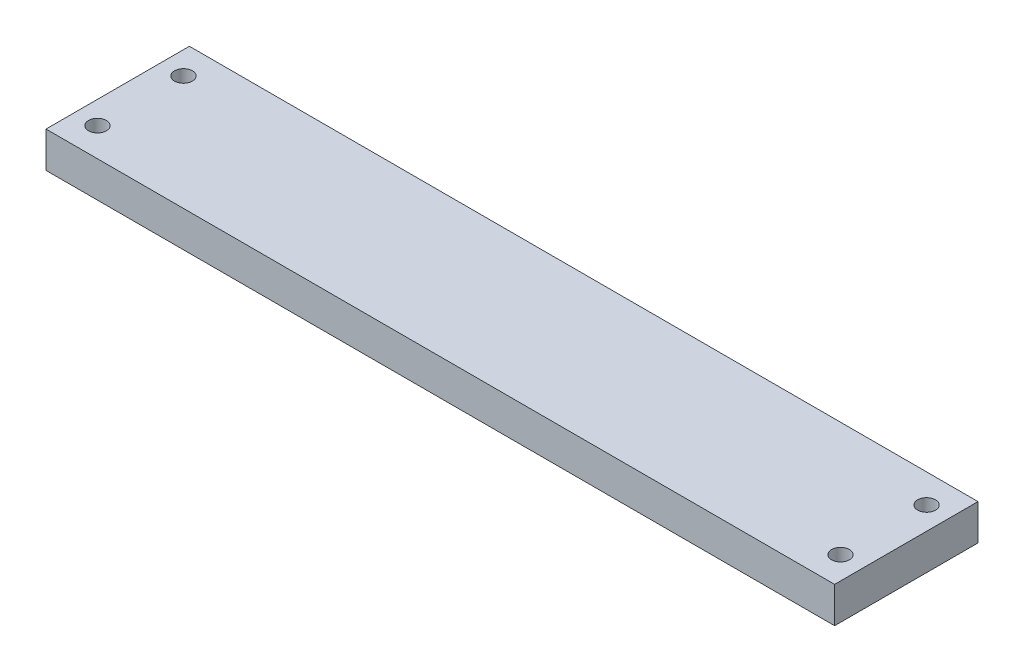
SolidWorks part; units mm, degrees
ref_plane "Front Plane" through (0, 0, 0) normal (0, 0, 1) x (1, 0, 0)
ref_plane "Top Plane" through (0, 0, 0) normal (0, 1, 0) x (1, 0, 0)
ref_plane "Right Plane" through (0, 0, 0) normal (1, 0, 0) x (0, 0, -1)
sketch "Sketch1" plane through (0, 0, 0) normal (0, 1, 0) x (1, 0, 0)
  line L5 (-55, -10) -> (55, -10)
  line L6 (-55, -10) -> (-55, 10)
  line L7 (-55, 10) -> (55, 10)
  line L8 (55, -10) -> (55, 10)
  line L9 (0, 10) -> (0, -10) construction
  line L10 (-55, 0) -> (55, 0) construction
  point P0 (0, 0)
  point P4 (0, 0)
  point P6 (0, 0)
  point P7 (0, 0)
  point P8 (0, 0)
  point P9 (0, 0)
  point P10 (0, 0)
  point P12 (0, 0)
  dimension "D1" = 20
  dimension "D2" = 110
extrude "Boss-Extrude1" add sketch "Sketch1" along normal mid plane 5
sketch "Sketch2" plane through (0, 2.5, 0) normal (0, 1, 0) x (1, 0, 0)
  line L0 (0, 10) -> (0, -10) construction
  line L1 (55, 10) -> (-55, 10) construction
  line L2 (-55, -10) -> (55, -10) construction
  line L3 (-55, 0) -> (55, 0) construction
  line L4 (-55, 10) -> (-55, -10) construction
  line L5 (55, -10) -> (55, 10) construction
  point P12 (-51.825, -6)
  point P13 (0, 0)
  point P14 (51.825, -6)
  point P15 (0, 0)
  point P16 (-51.825, 6)
  point P17 (51.825, 6)
  point P18 (0, 0)
  point P19 (0, 0)
  dimension "D1" = 103.65
  dimension "D2" = 4
hole_wizard "Tap Drill for M3x0.5 Tap1" positions "Sketch2" profile "Sketch3" hole size "M3x0.5" standard "ANSI Metric" end condition through all
sketch "Sketch3" plane through (51.825, 2.5, -6) normal (1, 0, 0) x (0, 0, 1)
  line L0 (0, 0) -> (0, 5)
  line L1 (0, 5) -> (1.25, 5)
  line L2 (1.25, 5) -> (1.25, 0)
  line L5 (1.25, 0) -> (0, 0)
  line L11 (0, -6.35) -> (0, 107.95) construction
  dimension "Thru Hole Dia." = 2.5
  dimension "Thru Hole Depth" = 5
